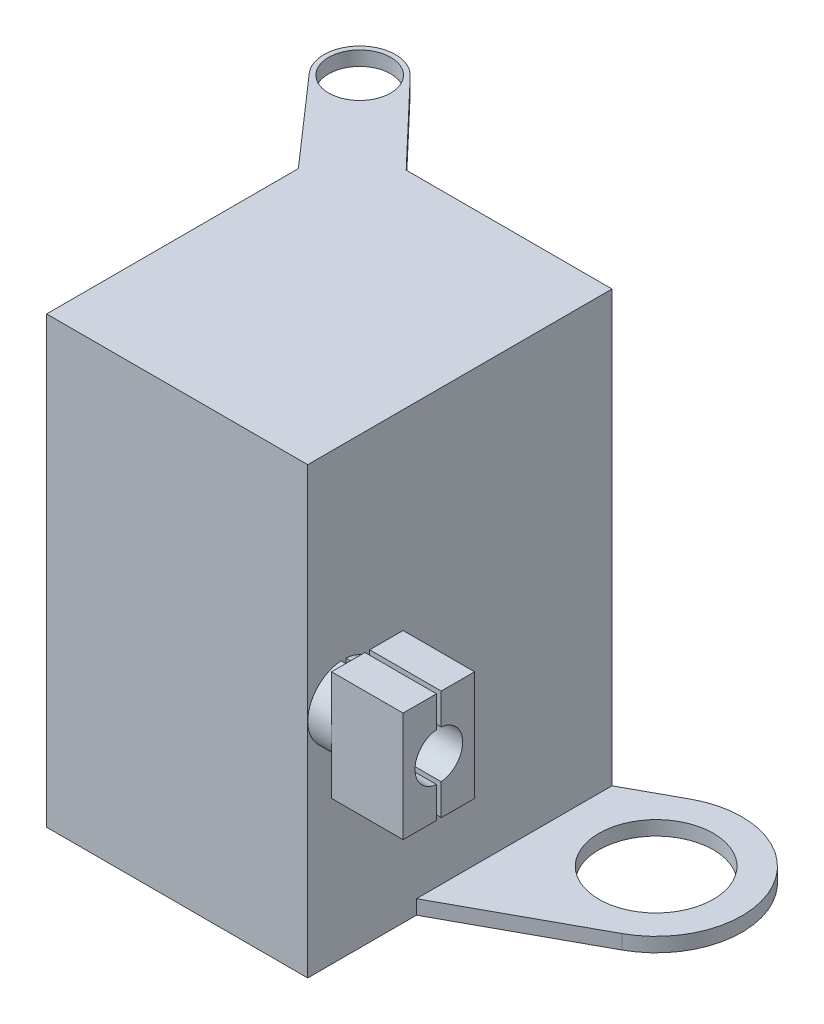
SolidWorks part; units mm, degrees
material "PET"
ref_plane "Front Plane" through (0, 0, 0) normal (0, 0, 1) x (1, 0, 0)
ref_plane "Top Plane" through (0, 0, 0) normal (0, 1, 0) x (1, 0, 0)
ref_plane "Right Plane" through (0, 0, 0) normal (1, 0, 0) x (0, 0, -1)
sketch "Sketch2" plane through (0, 0, 0) normal (0, 1, 0) x (1, 0, 0)
  line L0 (-25.4, 25.4) -> (-37.9, 50.8)
  line L1 (-25.4, -25.4) -> (25.4, -25.4)
  line L2 (-25.4, -25.4) -> (-25.4, 25.4) construction
  line L3 (-25.4, 25.4) -> (25.4, 25.4) construction
  line L4 (25.4, -25.4) -> (25.4, 25.4)
  line L5 (-25.4, -25.4) -> (25.4, 25.4) construction
  line L6 (-25.4, 25.4) -> (25.4, -25.4) construction
  line L7 (-43.5408, 45.8571) -> (-27.3672, 27.4)
  line L8 (-27.3672, 27.4) -> (-27.3672, -25.4)
  line L9 (-15.7761, 38.4294) -> (-32.4667, 55.97)
  line L10 (-15.7761, 38.4294) -> (25.4, 38.4294)
  line L11 (-15.7761, 38.4294) -> (-27.3672, 27.4) construction
  line L12 (-27.3672, -25.4) -> (-24.8672, -23.4)
  line L13 (25.4, -25.4) -> (27.4, -25.4)
  line L14 (25.4, -25.4) -> (25.4, 38.4294)
  line L15 (25.4, 38.4294) -> (27.4, 38.4294)
  line L16 (27.4, -25.4) -> (27.4, 38.4294)
  line L17 (-24.8672, -23.4) -> (25.4, -23.4)
  line L18 (-25.4, -25.4) -> (-27.3672, -25.4)
  circle A0 centre (-37.9, 50.8) radius 6.5
  circle A2 centre (-37.9, 50.8) radius 25
  circle A4 centre (-37.9, 50.8) radius 7.5
  point P0 (0, 0)
  dimension "D3" = 13
  dimension "D4" = 25.4
  dimension "D5" = 50
  dimension "D6" = 12.5
  dimension "D7" = 15
  dimension "D1" = 50.8
  dimension "D2" = 50.8
  dimension "D8" = 52.8
  dimension "D9" = 41.1761
  dimension "D10" = 16
  dimension "D11" = 2
  dimension "D12" = 2
  dimension "D13" = 2.5
extrude "Boss-Extrude1" add sketch "Sketch2" along normal blind 2 contours A4 L0 A2 L9 | A4 L7 A2 L0 | A4 A0 | A2 L7 L8 L12 L17 L14 L10 L9 | L13 L16 L15 L14 L4 | L18 L1 L4 L17 L12 region at (-33.9675, 0, -37.7193) region at (-0.5192, 0, -6.8997) region at (-25.8061, 0, -40.1072) region at (-39.3261, 0, -43.653) region at (-0.3636, 0, 24.4081) region at (26.4, 0, -6.5147)
extrude "Boss-Extrude2" add sketch "Sketch2<3>" along normal blind 90.25 contours L13 L16 L15 L4 | L17 L12 L1 L4 region at (-0.3636, 0, 24.4081) region at (26.4, 0, -6.5147)
sketch "Sketch2<3>" plane through (0, 0, 0) normal (0, 1, 0) x (1, 0, 0) same geometry as "Sketch2"
extrude "Boss-Extrude3" add sketch "Sketch2<4>" along normal blind 3 from surface contours A4 L7 A2 L0 | A4 L0 A2 L9 | A2 L7 L8 L12 L17 L14 L10 L9 | L18 L1 L4 L17 L12 | A4 A0 | L13 L16 L15 L14 region at (-33.9675, 0, -37.7193) region at (-0.5192, 0, -6.8997) region at (-25.8061, 0, -40.1072) region at (-39.3261, 0, -43.653) region at (-0.3636, 0, 24.4081) starting at face at (8.8943, 90.25, 3.4569)
sketch "Sketch2<4>" plane through (0, 0, 0) normal (0, 1, 0) x (1, 0, 0) same geometry as "Sketch2"
sketch "Sketch3" plane through (27.4, 0, 0) normal (1, 0, 0) x (0, 0, -1)
  line L0 (38.4294, 93.25) -> (38.4294, 0) construction
  line L1 (-18.4, 51.5999) -> (-18.4, 58.125)
  line L2 (-18.4, 58.125) -> (-25.4, 58.125)
  line L3 (-25.4, 58.125) -> (-25.4, 46.625)
  line L4 (-17.4, 51.5999) -> (-17.4, 58.125)
  line L5 (-17.4, 58.125) -> (-10.4, 58.125)
  line L6 (-10.4, 58.125) -> (-10.4, 46.625)
  line L7 (-18.4, 39.1417) -> (-18.4, 35.125)
  line L8 (-18.4, 35.125) -> (-25.4, 35.125)
  line L9 (-25.4, 35.125) -> (-25.4, 46.625)
  line L10 (-17.4, 39.1417) -> (-17.4, 35.125)
  line L11 (-17.4, 35.125) -> (-10.4, 35.125)
  line L12 (-10.4, 35.125) -> (-10.4, 46.625)
  line L13 (-18.4, 39.1417) -> (-18.4, 41.6501)
  line L14 (-17.4, 39.1417) -> (-17.4, 41.6501)
  line L15 (-25.4, 93.25) -> (-25.4, 0) construction
  circle A0 centre (-17.9, 46.625) radius 5
  circle A1 centre (-17.9, 46.625) radius 7.5
  point P0 (38.4294, 46.625)
  point P1 (0, 0)
  point P25 (1.6898, 29.4)
  dimension "D1" = 10
  dimension "D2" = 15
  dimension "D3" = 7
  dimension "D4" = 11.5
extrude "Boss-Extrude4" add sketch "Sketch3" along normal blind 20 contours A1 L4 A0 | A0 L1 A1 region at (27.4, 46.625, 23.0652) region at (27.4, 52.8541, 17.2348)
extrude "Boss-Extrude5" add sketch "Sketch3<3>" against normal blind 15 from surface contours A1 L9 L8 L7 | A1 L10 L11 L12 | L6 L5 L4 A1 | A1 L1 L2 L3 region at (27.4, 55.0179, 22.45) region at (27.4, 55.0179, 13.35) region at (27.4, 38.2321, 22.45) region at (27.4, 38.2321, 13.35) starting at face at (47.4, 46.625, 14.525)
sketch "Sketch3<3>" plane through (27.4, 0, 0) normal (1, 0, 0) x (0, 0, -1) same geometry as "Sketch3"
sketch "Sketch4" plane through (0, 0, 0) normal (0, -1, 0) x (1, 0, 0)
  line L1 (46.65, -50.6573) -> (65.9, -39.5434)
  line L2 (65.9, -39.5434) -> (65.9, -17.3154)
  line L3 (65.9, -17.3154) -> (46.65, -6.2014)
  line L4 (46.65, -6.2014) -> (27.4, -17.3154)
  line L5 (27.4, -17.3154) -> (27.4, -39.5434)
  line L6 (27.4, -39.5434) -> (46.65, -50.6573)
  line L7 (-15.7761, -38.4294) -> (27.4, -38.4294) construction
  line L8 (27.4, 25.4) -> (27.4, -38.4294) construction
  line L9 (38.0266, -44.2292) -> (27.4, -38.4294)
  line L10 (55.2734, -12.6295) -> (27.4, 2.5836)
  circle A0 centre (46.65, -28.4294) radius 18
  circle A1 centre (46.65, -28.4294) radius 19.25 construction
  circle A2 centre (46.65, -28.4294) radius 12
  point P19 (27.4, -9.3142)
  line M17 (27.4, -38.4294) -> (27.4, 25.4)
  dimension "D1" = 36
  dimension "D4" = 24
  dimension "D2" = 38.5
  dimension "D3" = 10
extrude "Boss-Extrude6" add sketch "Sketch4" against normal blind 3 contours A0 A2 | A0 L10 L4 L9 M17 | L4 L10 M17 region at (27.8644, 0, -27.8724) region at (33.3057, 0, -7.2727) region at (31.297, 0, -20.0498)
equation "\"x\"=38.1703"
